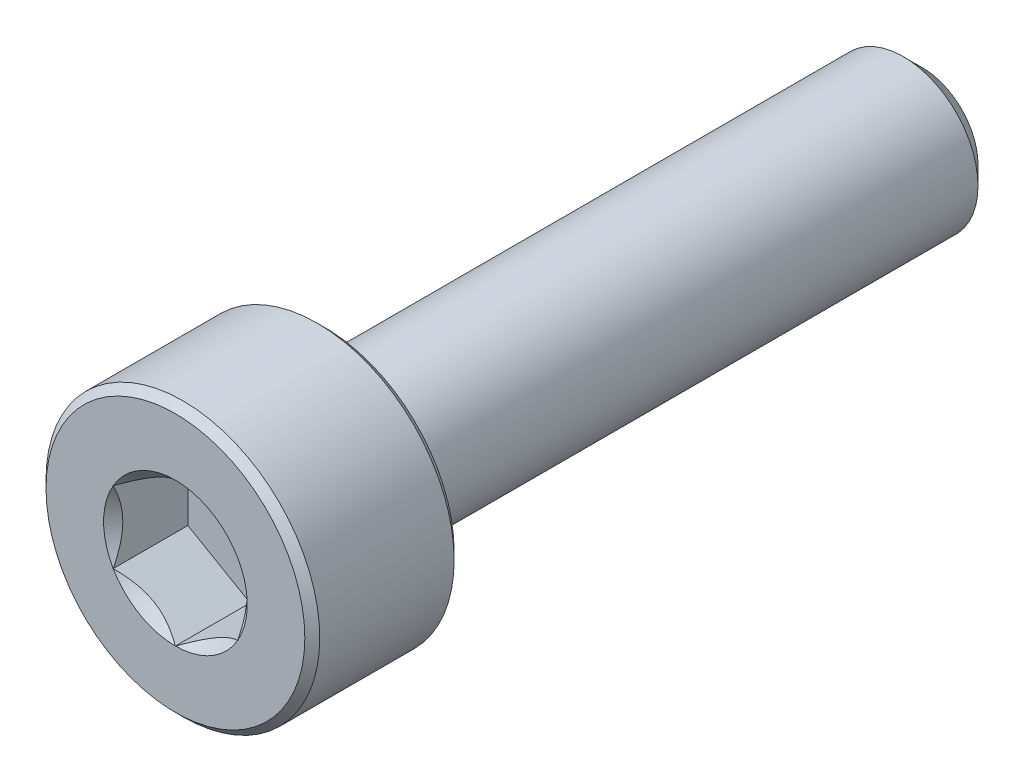
SolidWorks part; units mm, degrees
ref_plane "Front Plane" through (0, 0, 0) normal (0, 0, 1) x (1, 0, 0)
ref_plane "Top Plane" through (0, 0, 0) normal (0, 1, 0) x (1, 0, 0)
ref_plane "Right Plane" through (0, 0, 0) normal (1, 0, 0) x (0, 0, -1)
sketch "Sketch1" plane through (0, 0, 0) normal (1, 0, 0) x (0, 0, -1)
  line L0 (-7.5, 0) -> (7.5, 0) construction
  line L1 (7.5, 1.5) -> (7.5, -1.5) construction
  line L2 (-7.5, 1.25) -> (-7.5, -1.25) construction
  line L3 (-7.5, 2.75) -> (-7.5, -2.75) construction
  line L4 (-4.5, 2.75) -> (-4.5, -2.75) construction
  line L5 (7.4688, 1.5541) -> (7.7188, 1.1211) construction
  line L6 (7.7188, 1.1211) -> (7.9688, 1.5541) construction
  line L7 (7.9688, 1.5541) -> (7.4688, 1.5541) construction
  line L8 (7.7188, 1.5541) -> (7.7188, 1.5) construction
  line L9 (7.7188, 1.1211) -> (7.7188, 1.1752) construction
  line L10 (7.5, 1.5) -> (7.9375, 1.5) construction
  line L11 (7.4844, 1.5271) -> (7.9531, 1.5271)
  line L12 (7.6875, 1.1752) -> (7.75, 1.1752)
  point P3 (5.75, -1.5)
  point P4 (0, 0)
  point P8 (7.5, 0)
  point P10 (-7.5, 0)
  point P14 (-7.5, 0)
  point P17 (-4.5, 0)
  point P26 (7.7188, 1.5)
  point P29 (7.7188, 1.5271)
  point P31 (7.7188, 1.1752)
  point P32 (-6, 0)
  dimension "Pitch" = 0.5
  dimension "D2" = 0.0625
  dimension "Drive Size" = 2.5
  dimension "Head Diameter" = 5.5
  dimension "Head Height" = 3
  dimension "Length" = 12
  dimension "Thread Size" = 3
  dimension "D1" = 1.75
  dimension "D3" = 1.5
sketch "Sketch2" plane through (0, 0, 0) normal (1, 0, 0) x (0, 0, -1)
  line L0 (-7.5, 0) -> (-7.5, 2.75)
  line L1 (-7.5, 2.75) -> (-4.5, 2.75)
  line L2 (-4.5, 2.75) -> (-4.5, 1.5)
  line L3 (-4.5, 2.75) -> (-4.5, -2.75) construction
  line L4 (-4.5, 1.5) -> (7.125, 1.5)
  line L5 (7.125, 1.5) -> (7.5, 1.125)
  line L6 (7.5, 1.125) -> (7.5, 0)
  line L7 (7.5, 1.5) -> (7.5, -1.5) construction
  line L8 (-7.5, 0) -> (7.5, 0) construction
  line L9 (-7.5, 0) -> (7.5, 0)
  dimension "D1" = 45
  dimension "D2" = 0.375
revolve "Revolve1" add sketch "Sketch2" angle 360 about L9
sketch "Sketch3" plane through (0, 0, 7.5) normal (0, 0, 1) x (1, 0, 0)
  line L0 (0, 2.75) -> (0, -2.75) construction
  line L1 (0, 1.4434) -> (-1.25, 0.7217)
  line L2 (-1.25, 0.7217) -> (-1.25, -0.7217)
  line L3 (-1.25, -0.7217) -> (0, -1.4434)
  line L4 (0, -1.4434) -> (1.25, -0.7217)
  line L5 (1.25, -0.7217) -> (1.25, 0.7217)
  line L6 (1.25, 0.7217) -> (0, 1.4434)
  circle A0 centre (0, 0) radius 1.25 construction
extrude "Cut-Extrude1" cut sketch "Sketch3" against normal up to vertex (1.5 mm away) up to point (0, 0, 6)
sketch "Sketch4" plane through (0, 0, 7.5) normal (0, 0, 1) x (1, 0, 0)
  circle A0 centre (0, 0) radius 1.4434
extrude "Cut-Extrude2" cut sketch "Sketch4" against normal through all draft 45
chamfer "Chamfer1" distance 0.15 angle 45 2 edges at (2.75, 0, 4.5) (2.75, 0, 7.5)
split "Split1" [suppressed] bodies to split 107 108
sketch "Sketch6" [suppressed] plane through (0, 0, -7.5) normal (0, 0, -1) x (-1, 0, 0)
  circle A0 centre (0, 0) radius 1.5
  circle A1 centre (0, 0) radius 1.5 construction
  circle A2 centre (0, 0) radius 2.75 construction
curve "Helix/Spiral1" [suppressed] pitch 0.5 height 12.5 turns 25
sketch "Sketch7" [suppressed] plane through (0, 0, 0) normal (1, 0, 0) x (0, 0, -1)
  line L0 (7.4844, 1.5271) -> (7.6875, 1.1752)
  line L1 (7.6875, 1.1752) -> (7.75, 1.1752)
  line L2 (7.75, 1.1752) -> (7.9531, 1.5271)
  line L3 (7.9531, 1.5271) -> (7.4844, 1.5271)
sweep "Cut-Sweep1" [suppressed] cut profiles "Sketch7" path "Helix/Spiral1"
sketch "Sketch8" [suppressed] plane through (0, 0, 4.5) normal (0, 0, -1) x (-1, 0, 0)
  circle A1 centre (0, 0) radius 1.5
  circle A2 centre (0, 0) radius 1.5
  dimension "D1" = 0
extrude "Boss-Extrude1" [suppressed] add sketch "Sketch8" along normal up to next draft 15
equation "\"D2@Sketch1\"=\"Pitch@Sketch1\"/8"
equation "\"D2@Sketch2\"=\"Pitch@Sketch1\"*.75"
equation "\"D1@Sketch1\"=\"Pitch@Sketch1\"*3.50"
equation "\"D3@Sketch1\"=(\"Drive Size@Sketch1\"/2)*1.2"
equation "\"D4@Helix/Spiral1\"=\"Pitch@Sketch1\""
equation "\"D3@Helix/Spiral1\"=\"Length@Sketch1\"+\"Pitch@Sketch1\""
equation "\"D1@Chamfer1\"=\"Head Height@Sketch1\"/20"
